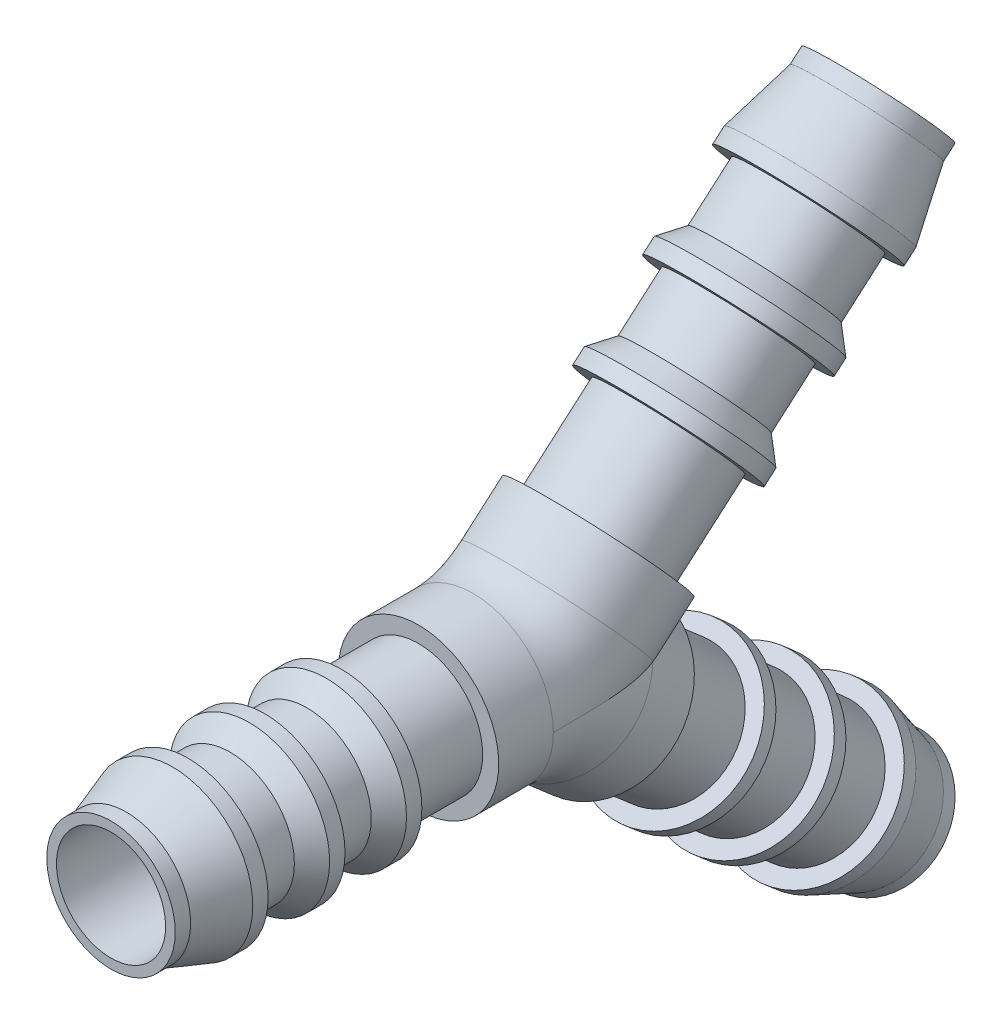
SolidWorks part; units mm, degrees
ref_plane "Front Plane" through (0, 0, 0) normal (0, 0, 1) x (1, 0, 0)
ref_plane "Top Plane" through (0, 0, 0) normal (0, 1, 0) x (1, 0, 0)
ref_plane "Right Plane" through (0, 0, 0) normal (1, 0, 0) x (0, 0, -1)
sketch "Sketch1" plane through (0, 0, 0) normal (1, 0, 0) x (0, 0, -1)
  line L0 (-30.4, 0) -> (30.4, 0) construction
  line L1 (0, 0) -> (26.503, 22.9496) construction
  line L2 (0, 0) -> (26.503, -22.9496) construction
  line L4 (-30.4, -5.9531) -> (-30.4, 5.9531) construction
  line L5 (30.4, 18.4493) -> (22.606, 27.45) construction
  line L6 (-30.4, -4.7625) -> (-30.4, 4.7625) construction
  line L7 (30.4, -18.4493) -> (22.606, -27.45) construction
  line L8 (29.6206, 19.3493) -> (23.3854, 26.5499) construction
  line L9 (-30.4, -4.0481) -> (-30.4, 4.0481) construction
  line L10 (29.153, 19.8894) -> (23.8531, 26.0099) construction
  circle A0 centre (0, 0) radius 7.6 construction
  point P7 (0, 0)
  point P10 (-30.4, 0)
  point P13 (-30.4, 0)
  point P14 (26.503, 22.9496)
  point P19 (-30.4, 0)
  point P22 (-30.4, 0)
  point P23 (26.503, -22.9496)
  point P27 (26.503, 22.9496)
  point P30 (-30.4, 0)
  point P33 (26.503, 22.9496)
  dimension "D4" = 15.2
  dimension "D2" = 40.89
  dimension "D1" = 11.9062
  dimension "D3" = 8.0962
sketch "Sketch11" plane through (0, 0, 0) normal (1, 0, 0) x (0, 0, -1)
  line L0 (-7.6, 0) -> (-7.6, 5.9531) construction
  line L1 (-30.4, 0) -> (30.4, 0) construction
  line L2 (-30.4, 4.0481) -> (-24.7, 4.0481) construction
  line L3 (-24.7, 4.0481) -> (-19, 4.0481) construction
  line L4 (-19, 4.0481) -> (-13.3, 4.0481) construction
  line L5 (-13.3, 4.0481) -> (-7.6, 4.0481) construction
  line L6 (-30.4, 4.0481) -> (-30.4, 5.9531) construction
  line L7 (-30.4, 4.7625) -> (-7.6, 4.7625) construction
  line L8 (-7.6, 5.9531) -> (-30.4, 5.9531) construction
  line L9 (-30.4, 4.0481) -> (-30.4, 4.7625)
  line L10 (-30.4, 4.7625) -> (-29.26, 4.7625)
  line L11 (-29.26, 4.7625) -> (-25.84, 5.9531)
  line L12 (-25.84, 5.9531) -> (-24.7, 5.9531)
  line L13 (-24.7, 5.9531) -> (-24.7, 4.7625)
  line L14 (-24.7, 4.7625) -> (-21.565, 4.7625)
  line L15 (-21.565, 4.7625) -> (-20.14, 5.9531)
  line L16 (-20.14, 5.9531) -> (-19, 5.9531)
  line L17 (-19, 5.9531) -> (-19, 4.7625)
  line L18 (-19, 4.7625) -> (-15.865, 4.7625)
  line L19 (-15.865, 4.7625) -> (-14.44, 5.9531)
  line L20 (-14.44, 5.9531) -> (-13.3, 5.9531)
  line L21 (-13.3, 5.9531) -> (-13.3, 4.7625)
  line L22 (-13.3, 4.7625) -> (-7.6, 4.7625)
  line L23 (-30.4, -5.9531) -> (-30.4, 5.9531) construction
  line L24 (-30.4, 4.0481) -> (-7.6, 4.0481)
  line L25 (-7.6, 4.0481) -> (-7.6, 4.7625)
  circle A0 centre (0, 0) radius 7.6 construction
  dimension "D1" = 22.8
  dimension "D2" = 1.14
  dimension "D3" = 1.425
revolve "Revolve1" add sketch "Sketch11" angle 360 about L0
sketch "Sketch12" plane through (0, 0, 0) normal (1, 0, 0) x (0, 0, -1)
  line L0 (5.7453, 4.975) -> (1.8484, 9.4754) construction
  line L2 (0, 0) -> (26.503, 22.9496) construction
  line L3 (22.606, 27.45) -> (1.8484, 9.4754) construction
  line L4 (23.8531, 26.0099) -> (18.6637, 21.5162) construction
  line L5 (18.6637, 21.5162) -> (13.4742, 17.0226) construction
  line L6 (13.4742, 17.0226) -> (8.2848, 12.5289) construction
  line L7 (8.2848, 12.5289) -> (3.0954, 8.0353) construction
  line L8 (30.4, 18.4493) -> (22.606, 27.45) construction
  line L9 (23.8531, 26.0099) -> (22.606, 27.45) construction
  line L10 (23.3854, 26.5499) -> (2.6278, 8.5753) construction
  line L11 (23.8531, 26.0099) -> (23.3854, 26.5499)
  line L12 (23.3854, 26.5499) -> (22.5236, 25.8037)
  line L13 (22.5236, 25.8037) -> (18.2784, 23.7026)
  line L14 (18.2784, 23.7026) -> (17.4166, 22.9564)
  line L15 (17.4166, 22.9564) -> (18.196, 22.0563)
  line L16 (18.196, 22.0563) -> (14.9457, 19.2417)
  line L17 (14.9457, 19.2417) -> (13.089, 19.209)
  line L18 (13.089, 19.209) -> (12.2272, 18.4627)
  line L19 (12.2272, 18.4627) -> (13.0066, 17.5626)
  line L20 (13.0066, 17.5626) -> (9.7562, 14.7481)
  line L21 (9.7562, 14.7481) -> (7.8996, 14.7153)
  line L22 (7.8996, 14.7153) -> (7.0378, 13.9691)
  line L23 (7.0378, 13.9691) -> (7.8172, 13.069)
  line L24 (7.8172, 13.069) -> (2.6278, 8.5753)
  line L25 (8.2848, 12.5289) -> (7.0378, 13.9691) construction
  line L26 (13.4742, 17.0226) -> (12.2272, 18.4627) construction
  line L27 (18.6637, 21.5162) -> (17.4166, 22.9564) construction
  line L28 (-30.4, 4.7625) -> (-29.26, 4.7625) construction
  line L29 (-21.565, 4.7625) -> (-20.14, 5.9531) construction
  line L30 (23.8531, 26.0099) -> (3.0954, 8.0353)
  line L31 (3.0954, 8.0353) -> (2.6278, 8.5753)
  circle A0 centre (0, 0) radius 7.6 construction
  point P5 (26.503, 22.9496)
revolve "Revolve2" add sketch "Sketch12" angle 360 about L1
sketch "Sketch13" plane through (0, 0, 0) normal (1, 0, 0) x (0, 0, -1)
  line L0 (-7.6, 0) -> (-3.5508, 0)
  line L1 (2.6843, 2.3244) -> (5.7453, 4.975)
  line L2 (0, 0) -> (26.503, 22.9496) construction
  circle A0 centre (0, 0) radius 7.6 construction
  arc A1 (2.6843, 2.3244) -> (-3.5508, 0) centre (-3.5508, 9.525) cw
  point P13 (0, 0)
  dimension "D1" = 9.525
sketch "Sketch14" plane through (0, 4.975, -5.7453) normal (0, -0.6546, 0.756) x (1, 0, 0)
  circle A1 centre (0, 0) radius 5.9531 construction
  circle A4 centre (0, 0) radius 5.9531
  circle A5 centre (0, 0) radius 4.0481 construction
  circle A6 centre (0, 0) radius 4.0481
sweep "Sweep7" add profiles "Sketch14" path "Sketch13"
sketch "Sketch15" plane through (0, 0, 0) normal (1, 0, 0) x (0, 0, -1)
  line L0 (-30.4, -5.9531) -> (-30.4, 5.9531) construction
  line L2 (-30.4, 0) -> (-30.4, -5.9531)
  line L3 (-30.4, -5.9531) -> (20.2667, -5.9531)
  line L5 (-30.4, 0) -> (20.2667, 0)
  line L7 (20.2667, 0) -> (20.2667, -5.9531)
  dimension "D1" = 20.2667
extrude "Cut-Extrude1" cut sketch "Sketch15" against normal through all both and the other way through all
move or copy body "Body-Move/Copy1" bodies to move or copy 110 copy yes number of copies 1 rotation origin (0, 0, 0) rotation axis (0, 0, 1) rotation angle 180
combine bodies "Combine1" operation type add bodies to combine 110 111
ref_axis "Center Axis 1" through (0, 0, 3.5508) along (0, 0, 1)
ref_axis "Center Axis 2" through (0, 2.4177, -2.792) along (0, 0.6546, -0.756)
ref_axis "Center Axis 3" through (0, -0.017, -0.0196) along (0, -0.6546, -0.756)
ref_plane "Contact Plane 1" through (0, 0, 30.4) normal (0, 0, 1) x (1, 0, 0)
ref_plane "Contact Plane 2" through (0, 22.9496, -26.503) normal (0, 0.6546, -0.756) x (-1, 0, 0)
ref_plane "Contact Plane 3" through (0, -22.9496, -26.503) normal (0, -0.6546, -0.756) x (-1, 0, 0)
equation "\"D1@Sketch1\"=\"ID@Sketch1\"*1.25"
equation "\"D4@Sketch1\"=\"L@Sketch1\"/4"
equation "\"D2@Sketch11\"=\"D1@Sketch11\"/20"
equation "\"D3@Sketch11\"=\"D2@Sketch11\"*1.25"
equation "\"D1@Sketch13\"=\"ID@Sketch1\""
equation "\"D1@Sketch15\"=\"L@Sketch1\"/3"
equation "\"D3@Sketch1\"=\"ID@Sketch1\"*0.85"
